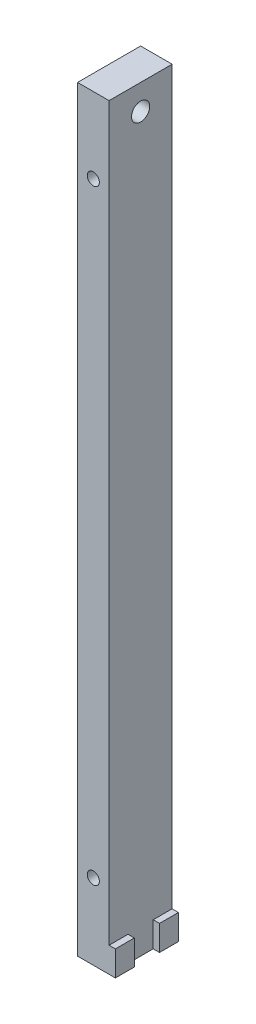
SolidWorks part; units mm, degrees
ref_plane "Front Plane" through (0, 0, 0) normal (0, 0, 1) x (1, 0, 0)
ref_plane "Top Plane" through (0, 0, 0) normal (0, 1, 0) x (1, 0, 0)
ref_plane "Right Plane" through (0, 0, 0) normal (1, 0, 0) x (0, 0, -1)
sketch "Sketch1" plane through (0, 0, 0) normal (0, 1, 0) x (1, 0, 0)
  line L0 (0, 0) -> (0, -15.875)
  line L1 (0, -15.875) -> (9.525, -15.875)
  line L2 (9.525, -15.875) -> (9.525, -11.1125)
  line L3 (9.525, -11.1125) -> (7.9375, -11.1125)
  line L4 (7.9375, -11.1125) -> (7.9375, -4.7625)
  line L5 (7.9375, -4.7625) -> (9.525, -4.7625)
  line L6 (9.525, -4.7625) -> (9.525, 0)
  line L7 (9.525, 0) -> (0, 0)
  dimension "D1" = 15.875
  dimension "D2" = 1.5875
  dimension "D3" = 6.35
  dimension "D4" = 9.525
extrude "Boss-Extrude1" add sketch "Sketch1" along normal blind 190.5
sketch "Sketch2" plane through (0, 190.5, 0) normal (0, 1, 0) x (1, 0, 0)
  line L0 (9.525, 0) -> (0, 0) construction
  line L1 (9.525, -15.875) -> (7.9375, -15.875)
  line L2 (9.525, -15.875) -> (9.525, 0)
  line L3 (9.525, 0) -> (7.9375, 0)
  line L4 (7.9375, -15.875) -> (7.9375, 0)
  line L5 (7.9375, -11.1125) -> (7.9375, -4.7625) construction
extrude "Cut-Extrude1" cut sketch "Sketch2" against normal offset from surface (184.15 mm away) 6.35 up to face at (6.7469, 0, 7.9375)
sketch "Sketch3" plane through (0, 0, 15.875) normal (0, 0, 1) x (1, 0, 0)
  line L0 (0, 190.5) -> (7.9375, 190.5) construction
  line L1 (0, 0) -> (9.525, 0) construction
  circle A0 centre (3.9687, 19.05) radius 1.524
  circle A1 centre (3.9687, 171.45) radius 1.524
  point P7 (3.9687, 190.5)
  dimension "D2" = 19.05
  dimension "D3" = 3.048
  dimension "D1" = 19.05
extrude "Cut-Extrude2" cut sketch "Sketch3" against normal through all
sketch "Sketch4" plane through (0, 0, 0) normal (-1, 0, 0) x (0, 0, 1)
  line L1 (0, 190.5) -> (15.875, 190.5) construction
  circle A0 centre (7.9375, 184.15) radius 2.286
  point P3 (7.9375, 190.5)
  dimension "D3" = 4.572
  dimension "D2" = 6.35
extrude "Cut-Extrude3" cut sketch "Sketch4" against normal through all
